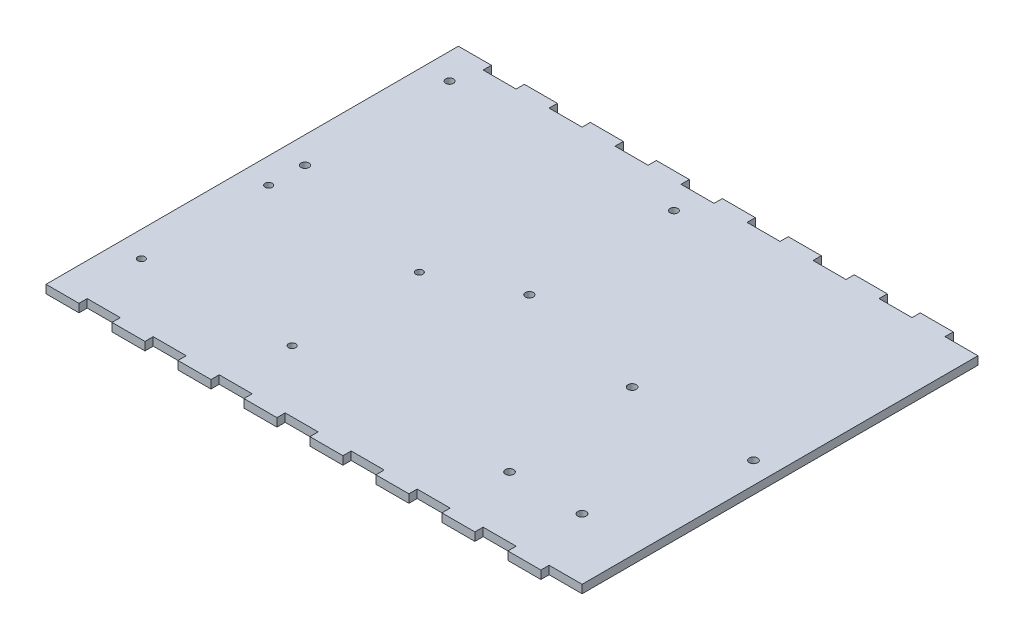
SolidWorks part; units mm, degrees
ref_plane "Front" through (0, 0, 0) normal (0, 0, 1) x (1, 0, 0)
ref_plane "Top" through (0, 0, 0) normal (0, 1, 0) x (1, 0, 0)
ref_plane "Right" through (0, 0, 0) normal (1, 0, 0) x (0, 0, -1)
sketch "Sketch1" plane through (0, 0, 0) normal (0, 1, 0) x (1, 0, 0)
  line L1 (0, 0) -> (203.2, 0)
  line L2 (0, 0) -> (0, 152.4)
  line L3 (0, 152.4) -> (203.2, 152.4)
  line L4 (203.2, 0) -> (203.2, 152.4)
  dimension "D1" = 203.2
  dimension "D2" = 152.4
extrude "Boss-Extrude1" add sketch "Sketch1" along normal blind 3.175
sketch "Sketch2" plane through (0, 3.175, 0) normal (0, 1, 0) x (1, 0, 0)
  line L0 (25.4, 0) -> (25.4, -3.175)
  line L1 (0, 0) -> (12.7, 0)
  line L2 (0, 0) -> (0, -3.175)
  line L3 (0, -3.175) -> (12.7, -3.175)
  line L4 (12.7, 0) -> (12.7, -3.175)
  line L5 (25.4, 0) -> (38.1, 0)
  line L6 (38.1, 0) -> (38.1, -3.175)
  line L7 (25.4, -3.175) -> (38.1, -3.175)
  line L8 (50.8, 0) -> (50.8, -3.175)
  line L9 (50.8, 0) -> (63.5, 0)
  line L10 (63.5, 0) -> (63.5, -3.175)
  line L11 (50.8, -3.175) -> (63.5, -3.175)
  line L12 (76.2, 0) -> (76.2, -3.175)
  line L13 (76.2, 0) -> (88.9, 0)
  line L14 (88.9, 0) -> (88.9, -3.175)
  line L15 (76.2, -3.175) -> (88.9, -3.175)
  line L16 (101.6, 0) -> (101.6, -3.175)
  line L17 (101.6, 0) -> (114.3, 0)
  line L18 (114.3, 0) -> (114.3, -3.175)
  line L19 (101.6, -3.175) -> (114.3, -3.175)
  line L20 (127, 0) -> (127, -3.175)
  line L21 (127, 0) -> (139.7, 0)
  line L22 (139.7, 0) -> (139.7, -3.175)
  line L23 (127, -3.175) -> (139.7, -3.175)
  line L24 (152.4, 0) -> (152.4, -3.175)
  line L25 (152.4, 0) -> (165.1, 0)
  line L26 (165.1, 0) -> (165.1, -3.175)
  line L27 (152.4, -3.175) -> (165.1, -3.175)
  line L28 (177.8, 0) -> (177.8, -3.175)
  line L29 (177.8, 0) -> (190.5, 0)
  line L30 (190.5, 0) -> (190.5, -3.175)
  line L31 (177.8, -3.175) -> (190.5, -3.175)
  line L32 (0, 76.2) -> (203.2, 76.2) construction
  line L33 (0, 152.4) -> (0, 0) construction
  line L34 (203.2, 0) -> (203.2, 152.4) construction
  line L35 (177.8, 152.4) -> (190.5, 152.4)
  line L36 (190.5, 152.4) -> (190.5, 155.575)
  line L37 (177.8, 155.575) -> (190.5, 155.575)
  line L38 (177.8, 152.4) -> (177.8, 155.575)
  line L39 (152.4, 152.4) -> (165.1, 152.4)
  line L40 (165.1, 152.4) -> (165.1, 155.575)
  line L41 (152.4, 155.575) -> (165.1, 155.575)
  line L42 (152.4, 152.4) -> (152.4, 155.575)
  line L43 (127, 152.4) -> (139.7, 152.4)
  line L44 (139.7, 152.4) -> (139.7, 155.575)
  line L45 (127, 155.575) -> (139.7, 155.575)
  line L46 (127, 152.4) -> (127, 155.575)
  line L47 (101.6, 152.4) -> (114.3, 152.4)
  line L48 (114.3, 152.4) -> (114.3, 155.575)
  line L49 (101.6, 155.575) -> (114.3, 155.575)
  line L50 (101.6, 152.4) -> (101.6, 155.575)
  line L51 (76.2, 152.4) -> (88.9, 152.4)
  line L52 (88.9, 152.4) -> (88.9, 155.575)
  line L53 (76.2, 155.575) -> (88.9, 155.575)
  line L54 (76.2, 152.4) -> (76.2, 155.575)
  line L55 (50.8, 152.4) -> (63.5, 152.4)
  line L56 (63.5, 152.4) -> (63.5, 155.575)
  line L57 (50.8, 155.575) -> (63.5, 155.575)
  line L58 (50.8, 152.4) -> (50.8, 155.575)
  line L59 (25.4, 152.4) -> (38.1, 152.4)
  line L60 (38.1, 152.4) -> (38.1, 155.575)
  line L61 (25.4, 155.575) -> (38.1, 155.575)
  line L62 (25.4, 152.4) -> (25.4, 155.575)
  line L63 (0, 155.575) -> (12.7, 155.575)
  line L64 (12.7, 152.4) -> (12.7, 155.575)
  line L65 (0, 152.4) -> (12.7, 152.4)
  line L66 (0, 152.4) -> (0, 155.575)
  dimension "D1" = 3.175
  dimension "D2" = 12.7
  dimension "D3" = 8
extrude "Boss-Extrude2" add sketch "Sketch2" against normal blind 3.175 separate body
sketch "Sketch4" plane through (-65.6185, 3.175, -114.5289) normal (0, 1, 0) x (1, 0, 0)
  line L0 (104.4685, -38.3289) -> (104.4685, -94.3289) construction
  line L1 (74.9685, -94.3289) -> (153.9685, -94.3289) construction
  line L2 (71.9685, -91.3289) -> (71.9685, -41.3289) construction
  line L3 (74.9685, -38.3289) -> (153.9685, -38.3289) construction
  line L4 (156.9685, -91.3289) -> (156.9685, -41.3289) construction
  line L10 (65.6185, 37.8711) -> (65.6185, -114.5289) construction
  line L12 (268.8185, 37.8711) -> (65.6185, 37.8711) construction
  arc A0 (74.9685, -94.3289) -> (71.9685, -91.3289) centre (74.9685, -91.3289) cw construction
  arc A1 (153.9685, -94.3289) -> (156.9685, -91.3289) centre (153.9685, -91.3289) ccw construction
  arc A2 (153.9685, -38.3289) -> (156.9685, -41.3289) centre (153.9685, -41.3289) cw construction
  arc A3 (71.9685, -41.3289) -> (74.9685, -38.3289) centre (74.9685, -41.3289) cw construction
  circle A4 centre (75.4685, -41.8289) radius 1.375
  circle A5 centre (75.4685, -90.8289) radius 1.375
  circle A6 centre (133.4685, -90.8289) radius 1.375
  circle A7 centre (133.4685, -41.8289) radius 1.375
  point P7 (71.9685, -94.3289)
  point P12 (156.9685, -38.3289)
  point P15 (71.9685, -38.3289)
  dimension "D3" = 3
  dimension "D4" = 2.75
  dimension "D1" = 56
  dimension "D2" = 85
  dimension "D5" = 49
  dimension "D6" = 3.5
  dimension "D7" = 3.5
  dimension "D8" = 58
  dimension "D9" = 6.35
  dimension "D10" = 76.2
extrude "Cut-Extrude1" cut sketch "Sketch4" against normal through all
sketch "Sketch5" plane through (-58.3327, 3.175, -175.8659) normal (0, 1, 0) x (0, 0, 1)
  line L0 (86.4754, 202.6489) -> (86.4754, 255.9489) construction
  line L1 (86.4754, 255.9489) -> (150.2443, 255.9489) construction
  line L2 (150.2443, 255.9489) -> (152.3754, 253.8178) construction
  line L3 (155.2754, 240.1078) -> (155.2754, 208.2989) construction
  line L4 (155.2754, 208.2989) -> (152.3754, 205.3989) construction
  line L5 (152.3754, 205.3989) -> (152.3754, 202.6489) construction
  line L6 (152.3754, 202.6489) -> (86.4754, 202.6489) construction
  line L7 (152.3754, 253.8178) -> (152.3754, 243.0078) construction
  line L8 (152.3754, 243.0078) -> (155.2754, 240.1078) construction
  circle A0 centre (100.4754, 205.3989) radius 1.6
  circle A1 centre (101.5754, 253.1989) radius 1.6
  circle A2 centre (152.3754, 210.0989) radius 1.6
  circle A3 centre (152.3754, 237.9989) radius 1.6
  dimension "D3" = 3.2
  dimension "D12" = 50.8
  dimension "D7" = 51.9
  dimension "D1" = 53.3
  dimension "D2" = 68.8
  dimension "D4" = 15.2
  dimension "D5" = 14
  dimension "D6" = 2.75
  dimension "D8" = 51.9
  dimension "D9" = 1.1
  dimension "D10" = 4.7
  dimension "D11" = 2.75
  dimension "D13" = 45
  dimension "D14" = 45
  dimension "D16" = 45
extrude "Cut-Extrude2" cut sketch "Sketch5" against normal through all
sketch "Sketch10" plane through (154.7382, 3.175, -89.7842) normal (0, 1, 0) x (0, 0, -1)
  line L0 (-4.9142, 54.3882) -> (53.9458, 54.3882) construction
  line L1 (-7.2342, 56.7082) -> (-7.2342, 146.0682) construction
  line L2 (-4.9142, 148.3882) -> (53.9458, 148.3882) construction
  line L3 (56.2658, 56.7082) -> (56.2658, 146.0682) construction
  line L4 (-7.2342, 54.3882) -> (56.2658, 148.3882) construction
  line L5 (-7.2342, 148.3882) -> (56.2658, 54.3882) construction
  line L6 (62.6158, 154.7382) -> (-89.7842, 154.7382) construction
  line L7 (62.6158, -48.4618) -> (62.6158, 154.7382) construction
  line L8 (-3.4238, 144.5682) -> (-3.4238, 58.2082) construction
  arc A0 (-4.9142, 54.3882) -> (-7.2342, 56.7082) centre (-4.9142, 56.7082) cw construction
  arc A1 (53.9458, 54.3882) -> (56.2658, 56.7082) centre (53.9458, 56.7082) ccw construction
  arc A2 (53.9458, 148.3882) -> (56.2658, 146.0682) centre (53.9458, 146.0682) cw construction
  arc A3 (-4.9142, 148.3882) -> (-7.2342, 146.0682) centre (-4.9142, 146.0682) ccw construction
  circle A4 centre (-66.0842, 86.8882) radius 1.375 construction
  circle A5 centre (-3.4238, 144.5682) radius 1.535
  circle A6 centre (52.4558, 144.7859) radius 1.5
  circle A7 centre (-3.4238, 58.2082) radius 1.535
  circle A8 centre (52.4558, 58.4259) radius 1.5
  point P0 (24.5158, 101.3882)
  dimension "D3" = 2.32
  dimension "D6" = 3.07
  dimension "D7" = 3
  dimension "D1" = 63.5
  dimension "D2" = 94
  dimension "D4" = 6.35
  dimension "D5" = 6.35
  dimension "D8" = 55.88
  dimension "D9" = 27.94
  dimension "D10" = 43.18
  dimension "D12" = 86.36
  dimension "D11" = 2
extrude "Cut-Extrude3" cut sketch "Sketch10" against normal through all both and the other way through all
combine bodies "Combine1" operation type add bodies to combine 102 104 106 108 110 112 114 116 117 122 103 105 107 109 111 113 115
